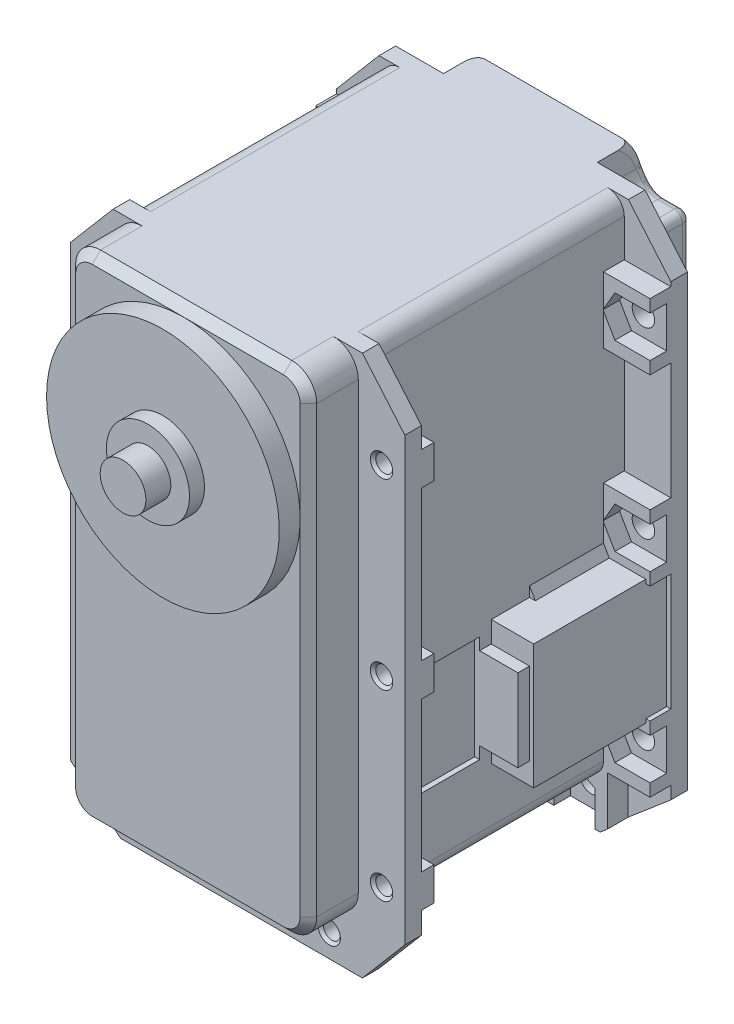
SolidWorks part; units mm, degrees
ref_plane "Front Plane" through (0, 0, 0) normal (0, 0, 1) x (1, 0, 0)
ref_plane "Top Plane" through (0, 0, 0) normal (0, 1, 0) x (1, 0, 0)
ref_plane "Right Plane" through (0, 0, 0) normal (1, 0, 0) x (0, 0, -1)
ref_plane "Plane1" through (9.25, 0, 0) normal (1, 0, 0) x (0, 0, -1)
sketch "Sketch1" plane through (9.25, 0, 0) normal (1, 0, 0) x (0, 0, -1)
  line L0 (21, 14.5) -> (21, 9.5)
  line L1 (21, 9.5) -> (23, 9.5)
  arc A0 (23, 9.5) -> (21, 14.5) centre (15.75, 9.5) ccw
extrude "Boss-Extrude1" add sketch "Sketch1" against normal blind 18.5
ref_plane "Plane2" through (0, 9.5, 0) normal (0, -1, 0) x (1, 0, 0)
sketch "Sketch2" plane through (0, 9.5, 0) normal (0, -1, 0) x (1, 0, 0)
  line L0 (-15.8711, -21) -> (-15.8711, -23)
  line L1 (-15.8711, -23) -> (-9.25, -23)
  line L2 (-9.25, -23) -> (-9.25, -21)
  line L3 (-9.25, -21) -> (-15.8711, -21)
extrude "Boss-Extrude2" add sketch "Sketch2" against normal blind 5
sketch "Sketch3" plane through (0, 9.5, 0) normal (0, -1, 0) x (1, 0, 0)
  line L0 (9.25, -21) -> (9.25, -23)
  line L1 (9.25, -23) -> (20.1, -23)
  line L2 (20.1, -23) -> (20.1, -21)
  line L3 (20.1, -21) -> (9.25, -21)
extrude "Boss-Extrude3" add sketch "Sketch3" against normal blind 5
sketch "Sketch4" plane through (0, 9.5, 0) normal (0, -1, 0) x (1, 0, 0)
  line L0 (20.1, -21) -> (20.1, -23)
  line L1 (20.1, -23) -> (-15.8711, -23)
  line L2 (-15.8711, -23) -> (-15.8711, -21)
  line L3 (-15.8711, -21) -> (20.1, -21)
extrude "Boss-Extrude4" add sketch "Sketch4" along normal blind 60.1
sketch "Sketch5" plane through (0, 0, -21) normal (0, 0, 1) x (1, 0, 0)
  line L0 (-15.8711, -50.6) -> (-15.8711, 14.5)
  line L1 (-15.8711, 14.5) -> (20.1, 14.5)
  line L2 (20.1, 14.5) -> (20.1, -50.6)
  line L3 (20.1, -50.6) -> (-15.8711, -50.6)
extrude "Boss-Extrude5" add sketch "Sketch5" along normal blind 6.5
sketch "Sketch6" plane through (0, 0, -23) normal (0, 0, -1) x (-1, 0, 0)
  line L0 (15.8711, -50.6) -> (15.8711, 14.5)
  line L1 (15.8711, 14.5) -> (9.25, 14.5)
  line L2 (9.25, 14.5) -> (9.25, -45)
  line L3 (9.25, -45) -> (-9.25, -45)
  line L4 (-9.25, -45) -> (-9.25, 14.5)
  line L5 (-9.25, 14.5) -> (-20.1, 14.5)
  line L6 (-20.1, 14.5) -> (-20.1, -50.6)
  line L7 (-20.1, -50.6) -> (15.8711, -50.6)
extrude "Cut-Extrude1" cut sketch "Sketch6" against normal blind 2
sketch "Sketch7" plane through (0, 0, -14.5) normal (0, 0, 1) x (1, 0, 0)
  line L0 (-15.8711, -20.475) -> (-14.5, -18.1003)
  line L1 (-14.5, -18.1003) -> (-14.5, -17.8997)
  line L2 (-14.5, -17.8997) -> (-15.8711, -15.525)
  line L3 (-15.8711, -15.525) -> (-15.8711, 1.525)
  line L4 (-15.8711, 1.525) -> (-14.5, 3.8997)
  line L5 (-14.5, 3.8997) -> (-14.5, 4.1003)
  line L6 (-14.5, 4.1003) -> (-15.8711, 6.475)
  line L7 (-15.8711, 6.475) -> (-15.8711, 14.5)
  line L8 (-15.8711, 14.5) -> (20.1, 14.5)
  line L9 (20.1, 14.5) -> (20.1, -50.6)
  line L10 (20.1, -50.6) -> (-15.8711, -50.6)
  line L11 (-15.8711, -50.6) -> (-15.8711, -42.475)
  line L12 (-15.8711, -42.475) -> (-14.5, -40.1003)
  line L13 (-14.5, -40.1003) -> (-14.5, -39.8997)
  line L14 (-14.5, -39.8997) -> (-15.8711, -37.525)
  line L15 (-15.8711, -37.525) -> (-15.8711, -20.475)
extrude "Boss-Extrude6" add sketch "Sketch7" along normal blind 2
sketch "Sketch8" plane through (0, 0, -21) normal (0, 0, -1) x (-1, 0, 0)
  line L0 (15.8711, -50.6) -> (15.8711, 14.5)
  line L1 (15.8711, 14.5) -> (9.25, 14.5)
  line L2 (9.25, 14.5) -> (9.25, -45)
  line L3 (9.25, -45) -> (-9.25, -45)
  line L4 (-9.25, -45) -> (-9.25, 14.5)
  line L5 (-9.25, 14.5) -> (-20.1, 14.5)
  line L6 (-20.1, 14.5) -> (-20.1, -50.6)
  line L7 (-20.1, -50.6) -> (15.8711, -50.6)
extrude "Cut-Extrude2" cut sketch "Sketch8" against normal blind 4
sketch "Sketch9" plane through (0, 0, -12.5) normal (0, 0, 1) x (1, 0, 0)
  line L0 (20.1, 14.5) -> (20.1, -50.6)
  line L1 (20.1, -50.6) -> (-15.8711, -50.6)
  line L2 (-15.8711, -50.6) -> (-15.8711, -42.475)
  line L3 (-15.8711, -42.475) -> (-14.5, -40.1003)
  line L4 (-14.5, -40.1003) -> (-14.5, 14.5)
  line L5 (-14.5, 14.5) -> (20.1, 14.5)
extrude "Boss-Extrude7" add sketch "Sketch9" along normal blind 29.5
sketch "Sketch10" plane through (0, 0, 17) normal (0, 0, 1) x (1, 0, 0)
  line L0 (14.5, 14.5) -> (14.5, -45)
  line L1 (14.5, -45) -> (-14.5, -45)
  line L2 (-14.5, -45) -> (-14.5, -40.1003)
  line L3 (-14.5, -40.1003) -> (-15.8711, -42.475)
  line L4 (-15.8711, -42.475) -> (-15.8711, -50.6)
  line L5 (-15.8711, -50.6) -> (20.1, -50.6)
  line L6 (20.1, -50.6) -> (20.1, 14.5)
  line L7 (20.1, 14.5) -> (14.5, 14.5)
extrude "Cut-Extrude3" cut sketch "Sketch10" against normal blind 29.5
sketch "Sketch11" plane through (0, 0, -12.5) normal (0, 0, 1) x (1, 0, 0)
  line L0 (-13.475, -50.6) -> (-8.525, -50.6)
  line L1 (-8.525, -50.6) -> (-8.525, -46.3711)
  line L2 (-8.525, -46.3711) -> (-11, -44.9421)
  line L3 (-11, -44.9421) -> (-13.475, -46.3711)
  line L4 (-13.475, -46.3711) -> (-13.475, -50.6)
extrude "Cut-Extrude4" cut sketch "Sketch11" against normal blind 2
sketch "Sketch12" plane through (0, 0, -12.5) normal (0, 0, 1) x (1, 0, 0)
  line L0 (20.1, 1.525) -> (20.1, 6.475)
  line L1 (20.1, 6.475) -> (15.8711, 6.475)
  line L2 (15.8711, 6.475) -> (14.4421, 4)
  line L3 (14.4421, 4) -> (15.8711, 1.525)
  line L4 (15.8711, 1.525) -> (20.1, 1.525)
extrude "Cut-Extrude5" cut sketch "Sketch12" against normal blind 2
sketch3d "3DSketch1"
  point P0 (0.3284, -15.6984, -2.5062)
  point P1 (0.3284, -115.6984, -2.5062)
ref_axis "Axis1" through (0.3284, -15.6984, -2.5062) along (0, -1, 0)
pattern_linear "LPattern1" count 3 spacing 22 along (0, -1, 0) of "Cut-Extrude5"
sketch "Sketch13" plane through (0, 0, -12.5) normal (0, 0, 1) x (1, 0, 0)
  line L0 (8.525, -50.6) -> (13.475, -50.6)
  line L1 (13.475, -50.6) -> (13.475, -46.3711)
  line L2 (13.475, -46.3711) -> (11, -44.9421)
  line L3 (11, -44.9421) -> (8.525, -46.3711)
  line L4 (8.525, -46.3711) -> (8.525, -50.6)
extrude "Cut-Extrude6" cut sketch "Sketch13" against normal blind 2
ref_plane "Plane3" through (0, 0, -14.5) normal (0, 0, -1) x (-1, 0, 0)
sketch "Sketch14" plane through (0, 0, -14.5) normal (0, 0, -1) x (-1, 0, 0)
  line L0 (14.4421, -40) -> (14.5, -40.1003)
  line L1 (14.5, -40.1003) -> (14.5, -39.8997)
  line L2 (14.5, -39.8997) -> (14.4421, -40)
extrude "Cut-Extrude7" cut sketch "Sketch14" against normal blind 2
sketch3d "3DSketch2"
  point P0 (0.2957, -15.6557, -2.4823)
  point P1 (0.2957, 84.3443, -2.4823)
ref_axis "Axis2" through (0.2957, -15.6557, -2.4823) along (0, 1, 0)
pattern_linear "LPattern2" count 3 spacing 22 along (0, 1, 0) of "Cut-Extrude7"
sketch "Sketch15" plane through (-15.8711, 0, 0) normal (-1, 0, 0) x (0, 0, 1)
  line L0 (-12.5, 14.5) -> (-12.5, 6.475)
  line L1 (-12.5, 6.475) -> (-14.5, 6.475)
  line L2 (-14.5, 6.475) -> (-14.5, 1.525)
  line L3 (-14.5, 1.525) -> (-12.5, 1.525)
  line L4 (-12.5, 1.525) -> (-12.5, -15.525)
  line L5 (-12.5, -15.525) -> (-14.5, -15.525)
  line L6 (-14.5, -15.525) -> (-14.5, -20.475)
  line L7 (-14.5, -20.475) -> (-12.5, -20.475)
  line L8 (-12.5, -20.475) -> (-12.5, -37.525)
  line L9 (-12.5, -37.525) -> (-14.5, -37.525)
  line L10 (-14.5, -37.525) -> (-14.5, -42.475)
  line L11 (-14.5, -42.475) -> (-12.5, -42.475)
  line L12 (-12.5, -42.475) -> (-12.5, -50.6)
  line L13 (-12.5, -50.6) -> (-17, -50.6)
  line L14 (-17, -50.6) -> (-17, 14.5)
  line L15 (-17, 14.5) -> (-12.5, 14.5)
extrude "Boss-Extrude8" add sketch "Sketch15" along normal blind 4.2289
sketch "Sketch16" plane through (-14.5, 0, 0) normal (-1, 0, 0) x (0, 0, 1)
  line L0 (15, -45) -> (15, 14.5)
  line L1 (15, 14.5) -> (17, 14.5)
  line L2 (17, 14.5) -> (17, -45)
  line L3 (17, -45) -> (15, -45)
extrude "Boss-Extrude9" add sketch "Sketch16" along normal blind 5.6
sketch "Sketch17" plane through (0, -45, 0) normal (0, -1, 0) x (1, 0, 0)
  line L0 (14.5, 15) -> (-20.1, 15)
  line L1 (-20.1, 15) -> (-20.1, 17)
  line L2 (-20.1, 17) -> (14.5, 17)
  line L3 (14.5, 17) -> (14.5, 15)
extrude "Boss-Extrude10" add sketch "Sketch17" along normal blind 5.6
sketch "Sketch18" plane through (14.5, 0, 0) normal (1, 0, 0) x (0, 0, -1)
  line L0 (-15, -50.6) -> (-17, -50.6)
  line L1 (-17, -50.6) -> (-17, 14.5)
  line L2 (-17, 14.5) -> (-15, 14.5)
  line L3 (-15, 14.5) -> (-15, -50.6)
extrude "Boss-Extrude11" add sketch "Sketch18" along normal blind 5.6
sketch "Sketch19" plane through (0, 0, -12.5) normal (0, 0, 1) x (1, 0, 0)
  line L0 (19.6, -36.5) -> (14.5, -36.5)
  line L1 (14.5, -36.5) -> (14.5, -21.5)
  line L2 (14.5, -21.5) -> (19.6, -21.5)
  line L3 (19.6, -21.5) -> (19.6, -36.5)
extrude "Boss-Extrude12" add sketch "Sketch19" along normal blind 13.5
sketch "Sketch20" plane through (0, 0, 1) normal (0, 0, 1) x (1, 0, 0)
  line L0 (19.1, -33.95) -> (14.5, -33.95)
  line L1 (14.5, -33.95) -> (14.5, -24.05)
  line L2 (14.5, -24.05) -> (19.1, -24.05)
  line L3 (19.1, -24.05) -> (19.1, -33.95)
extrude "Boss-Extrude13" add sketch "Sketch20" along normal blind 1.4
sketch "Sketch21" plane through (14.5, 0, 0) normal (1, 0, 0) x (0, 0, -1)
  line L0 (-2.4, -35.4) -> (-2.4, -22.6)
  line L1 (-2.4, -22.6) -> (-12.5, -22.6)
  line L2 (-12.5, -22.6) -> (-12.5, -35.4)
  line L3 (-12.5, -35.4) -> (-2.4, -35.4)
extrude "Cut-Extrude8" cut sketch "Sketch21" against normal blind 0.6
sketch "Sketch22" plane through (0, 0, -12.5) normal (0, 0, 1) x (1, 0, 0)
  line L0 (-19.6, -21.5) -> (-14.5, -21.5)
  line L1 (-14.5, -21.5) -> (-14.5, -36.5)
  line L2 (-14.5, -36.5) -> (-19.6, -36.5)
  line L3 (-19.6, -36.5) -> (-19.6, -21.5)
extrude "Boss-Extrude14" add sketch "Sketch22" along normal blind 13.5
sketch "Sketch23" plane through (0, 0, 1) normal (0, 0, 1) x (1, 0, 0)
  line L0 (-19.1, -24.05) -> (-14.5, -24.05)
  line L1 (-14.5, -24.05) -> (-14.5, -33.95)
  line L2 (-14.5, -33.95) -> (-19.1, -33.95)
  line L3 (-19.1, -33.95) -> (-19.1, -24.05)
extrude "Boss-Extrude15" add sketch "Sketch23" along normal blind 1.4
sketch "Sketch24" plane through (-14.5, 0, 0) normal (-1, 0, 0) x (0, 0, 1)
  line L0 (2.4, -22.6) -> (2.4, -35.4)
  line L1 (2.4, -35.4) -> (12.5, -35.4)
  line L2 (12.5, -35.4) -> (12.5, -22.6)
  line L3 (12.5, -22.6) -> (2.4, -22.6)
extrude "Cut-Extrude9" cut sketch "Sketch24" against normal blind 0.6
sketch "Sketch25" plane through (0, -50.6, 0) normal (0, -1, 0) x (1, 0, 0)
  line L0 (7.025, -15) -> (7.025, -12.5)
  line L1 (7.025, -12.5) -> (-7.025, -12.5)
  line L2 (-7.025, -12.5) -> (-7.025, -15)
  line L3 (-7.025, -15) -> (7.025, -15)
extrude "Cut-Extrude10" cut sketch "Sketch25" against normal blind 5.6
sketch "Sketch26" plane through (20.1, 0, 0) normal (1, 0, 0) x (0, 0, -1)
  line L0 (12.5, 7.975) -> (15, 7.975)
  line L1 (15, 7.975) -> (15, 14.5)
  line L2 (15, 14.5) -> (12.5, 14.5)
  line L3 (12.5, 14.5) -> (12.5, 7.975)
extrude "Cut-Extrude11" cut sketch "Sketch26" against normal blind 5.6
sketch "Sketch27" plane through (20.1, 0, 0) normal (1, 0, 0) x (0, 0, -1)
  line L0 (15, -21.975) -> (12.5, -21.975)
  line L1 (12.5, -21.975) -> (12.5, -36.025)
  line L2 (12.5, -36.025) -> (15, -36.025)
  line L3 (15, -36.025) -> (15, -21.975)
extrude "Cut-Extrude12" cut sketch "Sketch27" against normal blind 0.5
sketch "Sketch28" plane through (20.1, 0, 0) normal (1, 0, 0) x (0, 0, -1)
  line L0 (15, 0.025) -> (12.5, 0.025)
  line L1 (12.5, 0.025) -> (12.5, -14.025)
  line L2 (12.5, -14.025) -> (15, -14.025)
  line L3 (15, -14.025) -> (15, 0.025)
extrude "Cut-Extrude13" cut sketch "Sketch28" against normal blind 5.6
sketch "Sketch29" plane through (-20.1, 0, 0) normal (-1, 0, 0) x (0, 0, 1)
  line L0 (-15, 7.975) -> (-12.5, 7.975)
  line L1 (-12.5, 7.975) -> (-12.5, 14.5)
  line L2 (-12.5, 14.5) -> (-15, 14.5)
  line L3 (-15, 14.5) -> (-15, 7.975)
extrude "Cut-Extrude14" cut sketch "Sketch29" against normal blind 5.6
sketch "Sketch30" plane through (-20.1, 0, 0) normal (-1, 0, 0) x (0, 0, 1)
  line L0 (-12.5, 0.025) -> (-15, 0.025)
  line L1 (-15, 0.025) -> (-15, -14.025)
  line L2 (-15, -14.025) -> (-12.5, -14.025)
  line L3 (-12.5, -14.025) -> (-12.5, 0.025)
extrude "Cut-Extrude15" cut sketch "Sketch30" against normal blind 5.6
sketch "Sketch31" plane through (-20.1, 0, 0) normal (-1, 0, 0) x (0, 0, 1)
  line L0 (-15, -36.025) -> (-12.5, -36.025)
  line L1 (-12.5, -36.025) -> (-12.5, -21.975)
  line L2 (-12.5, -21.975) -> (-15, -21.975)
  line L3 (-15, -21.975) -> (-15, -36.025)
extrude "Cut-Extrude16" cut sketch "Sketch31" against normal blind 0.5
sketch "Sketch32" plane through (0, -45, 0) normal (0, -1, 0) x (1, 0, 0)
  line L0 (-13, 13.5) -> (-13, 15)
  line L1 (-13, 15) -> (-9, 15)
  line L2 (-9, 15) -> (-9, 13.5)
  line L3 (-9, 13.5) -> (-13, 13.5)
extrude "Boss-Extrude16" add sketch "Sketch32" along normal blind 5.6
sketch "Sketch33" plane through (0, -45, 0) normal (0, -1, 0) x (1, 0, 0)
  line L0 (9, 13.5) -> (9, 15)
  line L1 (9, 15) -> (13, 15)
  line L2 (13, 15) -> (13, 13.5)
  line L3 (13, 13.5) -> (9, 13.5)
extrude "Boss-Extrude17" add sketch "Sketch33" along normal blind 5.6
sketch "Sketch34" plane through (14.5, 0, 0) normal (1, 0, 0) x (0, 0, -1)
  line L0 (-13.5, 2) -> (-15, 2)
  line L1 (-15, 2) -> (-15, 6)
  line L2 (-15, 6) -> (-13.5, 6)
  line L3 (-13.5, 6) -> (-13.5, 2)
extrude "Boss-Extrude18" add sketch "Sketch34" along normal blind 5.6
sketch3d "3DSketch3"
  point P0 (0.0081, -16.3065, -2.1741)
  point P1 (0.0081, -116.3065, -2.1741)
ref_axis "Axis3" through (0.0081, -16.3065, -2.1741) along (0, -1, 0)
pattern_linear "LPattern3" count 3 spacing 22 along (0, -1, 0) of "Boss-Extrude18"
sketch "Sketch35" plane through (-14.5, 0, 0) normal (-1, 0, 0) x (0, 0, 1)
  line L0 (15, 2) -> (13.5, 2)
  line L1 (13.5, 2) -> (13.5, 6)
  line L2 (13.5, 6) -> (15, 6)
  line L3 (15, 6) -> (15, 2)
extrude "Boss-Extrude19" add sketch "Sketch35" along normal blind 5.6
pattern_linear "LPattern4" count 3 spacing 22 along (0, -1, 0) of "Boss-Extrude19"
sketch "Sketch36" plane through (0, 0, -17) normal (0, 0, -1) x (-1, 0, 0)
  line L0 (-14.5, 9.25) -> (-9.25, 9.25)
  line L1 (-9.25, 9.25) -> (-9.25, -39.75)
  line L2 (-9.25, -39.75) -> (-14.5, -39.75)
  line L3 (-14.5, -39.75) -> (-14.5, 9.25)
extrude "Boss-Extrude20" add sketch "Sketch36" along normal blind 6
sketch "Sketch37" plane through (0, 0, -17) normal (0, 0, -1) x (-1, 0, 0)
  line L0 (14.5, -39.75) -> (9.25, -39.75)
  line L1 (9.25, -39.75) -> (9.25, 9.25)
  line L2 (9.25, 9.25) -> (14.5, 9.25)
  line L3 (14.5, 9.25) -> (14.5, -39.75)
extrude "Boss-Extrude21" add sketch "Sketch37" along normal blind 6
sketch "Sketch38" plane through (0, 0, -12.5) normal (0, 0, 1) x (1, 0, 0)
  line L0 (14.5, -20.2876) -> (15.2, -21.5)
  line L1 (15.2, -21.5) -> (14.5, -21.5)
  line L2 (14.5, -21.5) -> (14.5, -20.2876)
extrude "Boss-Extrude22" add sketch "Sketch38" along normal blind 8.9
sketch "Sketch39" plane through (0, 0, -12.5) normal (0, 0, 1) x (1, 0, 0)
  line L0 (14.975, -43.975) -> (14.975, -50.6)
  line L1 (14.975, -50.6) -> (20.1, -50.6)
  line L2 (20.1, -50.6) -> (20.1, -43.975)
  line L3 (20.1, -43.975) -> (14.975, -43.975)
extrude "Cut-Extrude17" cut sketch "Sketch39" against normal blind 2.5
sketch "Sketch40" plane through (0, -50.6, 0) normal (0, -1, 0) x (1, 0, 0)
  line L0 (-20.1, -15) -> (-14.975, -15)
  line L1 (-14.975, -15) -> (-14.975, -12.5)
  line L2 (-14.975, -12.5) -> (-20.1, -12.5)
  line L3 (-20.1, -12.5) -> (-20.1, -15)
extrude "Cut-Extrude18" cut sketch "Sketch40" against normal blind 6.625
sketch "Sketch41" plane through (0, 0, 17) normal (0, 0, 1) x (1, 0, 0)
  line L0 (-14.5, -45) -> (-14.5, 14.5)
  line L1 (-14.5, 14.5) -> (14.5, 14.5)
  line L2 (14.5, 14.5) -> (14.5, -45)
  line L3 (14.5, -45) -> (-14.5, -45)
extrude "Boss-Extrude23" add sketch "Sketch41" along normal blind 6
sketch "Sketch42" plane through (0, 0, -12.5) normal (0, 0, 1) x (1, 0, 0)
  line L0 (-14.5, -20.2876) -> (-14.5, -21.5)
  line L1 (-14.5, -21.5) -> (-15.2, -21.5)
  line L2 (-15.2, -21.5) -> (-14.5, -20.2876)
extrude "Boss-Extrude24" add sketch "Sketch42" along normal blind 8.9
sketch "Sketch43" plane through (-14.5, 0, 0) normal (-1, 0, 0) x (0, 0, 1)
  line L0 (-5, -13.45) -> (-5, -7.55)
  line L1 (-5, -7.55) -> (-8.8, -7.55)
  line L2 (-8.8, -7.55) -> (-8.8, -13.45)
  line L3 (-8.8, -13.45) -> (-5, -13.45)
extrude "Cut-Extrude19" cut sketch "Sketch43" against normal blind 1
hole_wizard "Ø15.0 (15) Diameter Hole1" positions "Sketch45" profile "Sketch44" hole size "Ø15.0" standard "ANSI Metric"
sketch "Sketch45" plane through (0, 0, -23) normal (0, 0, -1) x (-1, 0, 0)
  point P0 (0, 0)
sketch "Sketch44" plane through (0, 0, -23) normal (1, 0, 0) x (0, 1, 0)
  line L0 (0, 0) -> (0, 1)
  line L1 (0, 1) -> (7.5, 1)
  line L2 (7.5, 1) -> (7.5, 0)
  line L5 (7.5, 0) -> (0, 0)
  line L10 (0, 1) -> (-7.5, 1) construction
  line L11 (0, -6.35) -> (0, 107.95) construction
  dimension "Hole Dia." = 15
  dimension "Hole Depth" = 1
  dimension "Drill Angle" = 180
ref_plane "Plane4" through (0, 0, 0) normal (0, -1, 0) x (1, 0, 0)
sketch "Sketch46" plane through (0, 0, 0) normal (0, -1, 0) x (1, 0, 0)
  line L0 (2.75, 30.8) -> (0, 30.8)
  line L1 (0, 30.8) -> (0, 23)
  line L2 (0, 23) -> (9, 23)
  line L3 (9, 23) -> (9, 23.5)
  line L4 (9, 23.5) -> (14, 23.5)
  line L5 (14, 23.5) -> (14, 26)
  line L6 (14, 26) -> (5, 26)
  line L7 (5, 26) -> (5, 27.8)
  line L8 (5, 27.8) -> (2.75, 27.8)
  line L9 (2.75, 27.8) -> (2.75, 30.8)
  line L10 (0, 30.8) -> (0, 23) construction
revolve "Revolve1" add sketch "Sketch46" angle 360 about L10 reverse direction yes
sketch "Sketch47" plane through (0, 0, 0) normal (0, -1, 0) x (1, 0, 0)
  line L0 (5, -22) -> (0, -22)
  line L1 (0, -22) -> (0, -24.5)
  line L2 (0, -24.5) -> (4, -24.5)
  line L3 (4, -24.5) -> (4, -22.3)
  line L4 (4, -22.3) -> (5, -22.3)
  line L5 (5, -22.3) -> (5, -22)
  line L6 (0, -22) -> (0, -24.5) construction
revolve "Revolve2" add sketch "Sketch47" angle 360 about L6 reverse direction yes
hole_wizard "Ø2.7 (2.7) Diameter Hole1" positions "Sketch49" profile "Sketch48" hole size "Ø2.7" standard "ANSI Metric"
sketch "Sketch49" plane through (0, 0, -14.5) normal (0, 0, 1) x (1, 0, 0)
  point P0 (-17.3, 4)
  point P1 (-17.3, -18)
  point P2 (-11, -47.8)
  point P3 (17.3, 4)
  point P4 (17.3, -18)
  point P5 (11, -47.8)
  point P6 (-17.3, -40)
  point P7 (17.3, -40)
sketch "Sketch48" plane through (-17.3, 4, -14.5) normal (1, 0, 0) x (0, -1, 0)
  line L0 (0, 0) -> (0, 10)
  line L1 (0, 10) -> (1.35, 10)
  line L2 (1.35, 10) -> (1.35, 0)
  line L5 (1.35, 0) -> (0, 0)
  line L11 (0, -6.35) -> (0, 107.95) construction
  dimension "Thru Hole Dia." = 2.7
  dimension "Thru Hole Depth" = 10
hole_wizard "Ø2.05 (2.05) Diameter Hole1" positions "Sketch51" profile "Sketch50" hole size "Ø2.05" standard "ANSI Metric"
sketch "Sketch51" plane through (0, 0, 17) normal (0, 0, 1) x (1, 0, 0)
  point P0 (17.3, 4)
  point P1 (17.3, -18)
  point P2 (17.3, -40)
  point P3 (11, -47.8)
  point P4 (-17.3, 4)
  point P5 (-17.3, -18)
  point P6 (-17.3, -40)
  point P7 (-11, -47.8)
sketch "Sketch50" plane through (17.3, 4, 17) normal (1, 0, 0) x (0, -1, 0)
  line L0 (0, 0) -> (0, 41.5)
  line L1 (0, 41.5) -> (1.025, 41.5)
  line L2 (1.025, 41.5) -> (1.025, 0)
  line L5 (1.025, 0) -> (0, 0)
  line L11 (0, -6.35) -> (0, 107.95) construction
  dimension "Thru Hole Dia." = 2.05
  dimension "Thru Hole Depth" = 41.5
hole_wizard "Ø3.2 (3.2) Diameter Hole1" positions "Sketch53" profile "Sketch52" hole size "Ø3.2" standard "ANSI Metric"
sketch "Sketch53" plane through (0, 0, -24.5) normal (0, 0, -1) x (-1, 0, 0)
  point P0 (0, 0)
sketch "Sketch52" plane through (0, 0, -24.5) normal (1, 0, 0) x (0, 1, 0)
  line L0 (0, 0) -> (0, 2.2)
  line L1 (0, 2.2) -> (1.6, 2.2)
  line L2 (1.6, 2.2) -> (1.6, 0)
  line L5 (1.6, 0) -> (0, 0)
  line L10 (0, 2.2) -> (-1.6, 2.2) construction
  line L11 (0, -6.35) -> (0, 107.95) construction
  dimension "Hole Dia." = 3.2
  dimension "Hole Depth" = 2.2
  dimension "Drill Angle" = 180
fillet "Fillet1" radius 2 4 edges at (14.5, 14.5, 0) (14.5, -45, 1.25) (-14.5, -45, 1.25) tangent propagation no
fillet "Fillet2" radius 2.25 4 edges at (-9.25, -39.75, -20) (9.25, -39.75, -20) (9.25, 9.25, -20) (-9.25, 9.25, -20) tangent propagation no
fillet "Fillet3" radius 3 4 edges at (-14.5, -45, 20) (14.5, -45, 20) tangent propagation no
chamfer "Chamfer1" distance 0.325 angle 45 8 edges at (18.325, 4, 17) (18.325, -40, 17) (12.025, -47.8, 17) (-16.275, 4, 17) (-16.275, -18, 17) (-16.275, -40, 17) (-9.975, -47.8, 17) (18.325, -18, 17)
chamfer "Chamfer2" distance 5.1 angle 49.635 2 edges at (20.1, 14.5, -16) (-20.1, -50.6, -16) first distance on face at (-0.0325, 14.5, 0.4) first distance on face at (0, -50.6, -14.1)
chamfer "Chamfer3" distance 5.1 angle 49.635 2 edges at (20.1, -50.6, 16) (-20.1, 14.5, 16) first distance on face at (0, -50.6, 14.8333) first distance on face at (-0.5425, 14.5, 0.4)
chamfer "Chamfer4" distance 6 angle 40.365 2 edges at (20.1, -50.6, -16) (-20.1, 14.5, -16) first distance on face at (0.51, -50.6, -14.1) first distance on face at (-20.1, -17.5786, -13.9643)
chamfer "Chamfer5" distance 6 angle 40.365 2 edges at (-20.1, -50.6, 16) (20.1, 14.5, 16) first distance on face at (-0.85, -50.6, 14.8333) first distance on face at (20.1, -17.2625, 14.6875)
chamfer "Chamfer6" distance 1 angle 45 8 edges at (13.6213, 13.6213, 23) (0, 14.5, 23) (14.5, -15.25, 23) (-13.6213, 13.6213, 23) (13.6213, -44.1213, 23) (-14.5, -15.25, 23) (0, -45, 23) (-13.6213, -44.1213, 23)
fillet "Fillet4" radius 1 37 edges at (-9.455, 10.5616, -22.9219) (-10.9697, 9.3134, -23) (-13, 9.25, -23) (-14.5, 9.25, -20) (-14.5, -15.25, -23) (-14.5, -39.75, -20) (-9.909, -40.409, -23) (-13, -39.75, -23) (-9.25, -45, -20) (9.25, -45, -20) (0, -45, -23) (14.5, -39.75, -20) (9.909, -40.409, -23) (13, -39.75, -23) (14.5, -15.25, -23) (14.5, 9.25, -20) (13, 9.25, -23) (10.9697, 9.3134, -23) (9.7149, 10.1304, -22.9725) (-14.5, -20, 14.25) (14.5, -20, 14.25) (-14.5, 2, 14.25) (14.5, 2, 14.25) (-14.5, 6, 14.25) (-14.5, -38, 14.25) (-14.5, -16, 14.25) (14.5, 6, 14.25) (14.5, -16, 14.25) (14.5, -38, 14.25) (9, -45, 14.25) (-9, -45, 14.25) (-13, -44.9365, 14.25) (13, -44.9365, 14.25) tangent propagation no
